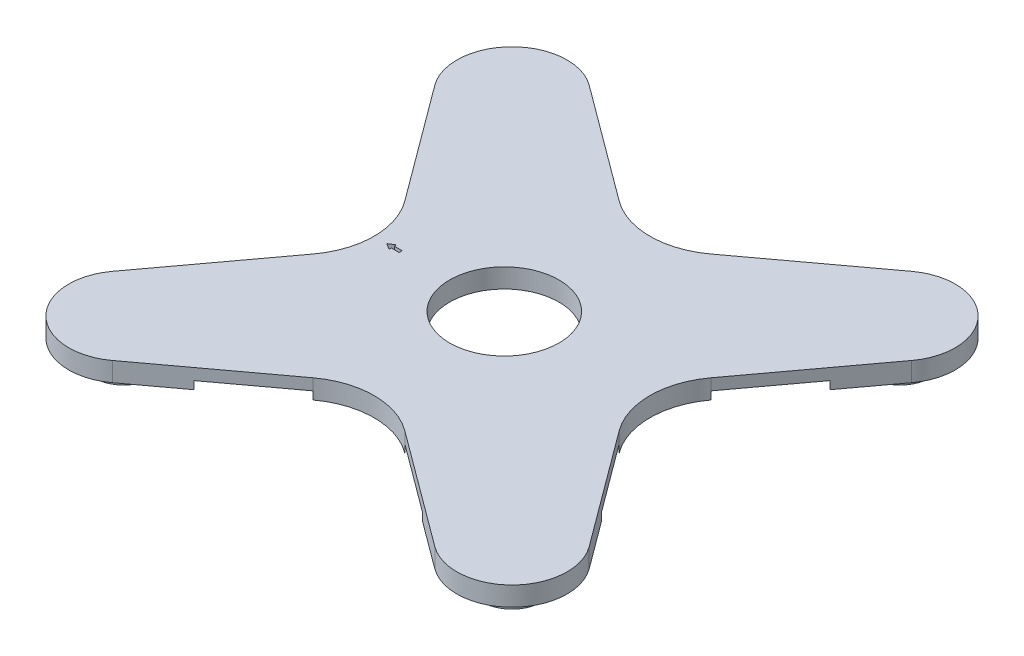
SolidWorks part; units mm, degrees
ref_plane "Front Plane" through (0, 0, 0) normal (0, 0, 1) x (1, 0, 0)
ref_plane "Top Plane" through (0, 0, 0) normal (0, 1, 0) x (1, 0, 0)
ref_plane "Right Plane" through (0, 0, 0) normal (1, 0, 0) x (0, 0, -1)
sketch "Sketch1" plane through (0, 0, 0) normal (0, 1, 0) x (1, 0, 0)
  line L0 (-25.2318, 7.5541) -> (-39.3151, 26.5872)
  line L1 (-26.5872, 39.3151) -> (-7.5541, 25.2318)
  line L2 (7.5541, 25.2318) -> (26.5872, 39.3151)
  line L3 (39.3151, 26.5872) -> (25.2318, 7.5541)
  line L4 (25.2318, -7.5541) -> (39.3151, -26.5872)
  line L5 (26.5872, -39.3151) -> (7.5541, -25.2318)
  line L6 (-7.5541, -25.2318) -> (-26.5872, -39.3151)
  line L7 (-39.3151, -26.5872) -> (-25.2318, -7.5541)
  line L8 (-32, 32) -> (32, -32) construction
  line L9 (-32, -32) -> (32, 32) construction
  line L10 (-32, -32) -> (32, -32) construction
  line L11 (-32, 32) -> (-32, -32) construction
  line L12 (-32, 32) -> (32, 32) construction
  line L13 (32, 32) -> (32, -32) construction
  line L14 (-25.2318, -7.5541) -> (-7.5541, -25.2318) construction
  line L15 (-25.2318, 7.5541) -> (-7.5541, 25.2318) construction
  line L16 (7.5541, 25.2318) -> (25.2318, 7.5541) construction
  line L17 (25.2318, -7.5541) -> (7.5541, -25.2318) construction
  line L25 (-19.6422, 0.254) -> (-18.3722, 0.254)
  line L26 (-19.6422, 0.254) -> (-19.6422, -0.254)
  line L27 (-19.6422, -0.254) -> (-18.3722, -0.254)
  line L28 (-18.3722, 0.254) -> (-18.3722, -0.254)
  line L29 (-19.6422, -0.635) -> (-20.6582, 0)
  line L30 (-20.6582, 0) -> (-19.6422, 0.635)
  line L31 (-19.6422, 0.635) -> (-19.6422, -0.635)
  circle A0 centre (0, 0) radius 7.9375 construction
  circle A1 centre (0, 0) radius 9.525 construction
  circle A2 centre (-1.27, 0) radius 9.017
  arc A3 (-39.3151, 26.5872) -> (-26.5872, 39.3151) centre (-32, 32) cw
  arc A4 (-7.5541, 25.2318) -> (7.5541, 25.2318) centre (0, 19.6422) cw
  arc A5 (26.5872, 39.3151) -> (39.3151, 26.5872) centre (32, 32) cw
  arc A6 (25.2318, 7.5541) -> (25.2318, -7.5541) centre (19.6422, 0) cw
  arc A7 (39.3151, -26.5872) -> (26.5872, -39.3151) centre (32, -32) cw
  arc A8 (7.5541, -25.2318) -> (-7.5541, -25.2318) centre (0, -19.6422) cw
  arc A9 (-26.5872, -39.3151) -> (-39.3151, -26.5872) centre (-32, -32) cw
  arc A10 (-25.2318, -7.5541) -> (-25.2318, 7.5541) centre (-19.6422, 0) cw
  circle A11 centre (-32, 32) radius 5
  circle A12 centre (32, 32) radius 5
  circle A13 centre (-32, -32) radius 5
  circle A14 centre (32, -32) radius 5
  arc A15 (-25.2318, 7.5541) -> (-25.2318, -7.5541) centre (-35.4409, 0) cw
  arc A16 (-7.5541, -25.2318) -> (7.5541, -25.2318) centre (0, -35.4409) cw
  arc A17 (-7.5541, 25.2318) -> (7.5541, 25.2318) centre (0, 35.4409) ccw
  arc A18 (25.2318, -7.5541) -> (25.2318, 7.5541) centre (35.4409, 0) cw
  point P34 (-16.3929, -16.3929)
  point P35 (16.3929, -16.3929)
  point P36 (-16.3929, 16.3929)
  point P37 (16.3929, 16.3929)
  point P38 (0, 0)
  point P47 (-19.6422, 0)
  point P51 (-19.6422, 0)
  point P52 (-19.6422, -1.0249)
  point P53 (0, 0)
  point P54 (-20.9244, 0)
  point P55 (-20.9244, 0)
  point P56 (-20.9244, 0)
  point P57 (-17.7372, -0.254)
  point P58 (-19.6422, 0)
  point P59 (-20.6582, 0)
  point P60 (-19.6422, 0.635)
  dimension "D1" = 15.875
  dimension "D2" = 19.05
  dimension "D3" = 18.034
  dimension "D6" = 10
  dimension "D9" = 12.7
  dimension "D4" = 1.27
  dimension "D5" = 64
  dimension "D7" = 18
  dimension "D8" = 25
  dimension "D10" = 0.508
  dimension "D11" = 1.27
  dimension "D12" = 1.27
  dimension "D13" = 1.016
extrude "Boss-Extrude1" add sketch "Sketch1" along normal blind 3.175 contours L4 A18 L3 A5 L2 A17 L1 A3 L0 A15 L7 A9 L6 A16 L5 A7 A14 A13 A12 A11 A2 region at (-31.339, 0, -17.7621)
extrude "Boss-Extrude2" add sketch "Sketch1<3>" against normal blind 6.35 from surface contours A11 | A14 | A12 | A13 region at (-32, 0, -32) region at (32, 0, -32) region at (-32, 0, 32) region at (32, 0, 32) starting at face at (32, 3.175, 37)
sketch "Sketch1<3>" plane through (0, 0, 0) normal (0, 1, 0) x (1, 0, 0) same geometry as "Sketch1"
sketch "Sketch2" plane through (0, 0, 0) normal (0, -1, 0) x (1, 0, 0)
  line L0 (-6.4623, -24.4239) -> (-24.4239, -6.4623)
  line L1 (-26.5872, -39.3151) -> (-7.5541, -25.2318) construction
  line L2 (-25.2318, -7.5541) -> (-39.3151, -26.5872) construction
  line L3 (-24.4239, -6.4623) -> (-33.5895, -18.8493)
  line L4 (-33.5895, -18.8493) -> (-18.8493, -33.5895)
  line L5 (-18.8493, -33.5895) -> (-6.4623, -24.4239)
  line L6 (-15.4431, -15.4431) -> (-32, -32) construction
  line L7 (3.4925, 0) -> (-3.4925, 0) construction
  line L8 (-33.5895, 18.8493) -> (-18.8493, 33.5895)
  line L9 (-24.4239, 6.4623) -> (-33.5895, 18.8493)
  line L10 (-6.4623, 24.4239) -> (-24.4239, 6.4623)
  line L11 (-18.8493, 33.5895) -> (-6.4623, 24.4239)
  line L12 (0, -3.4925) -> (0, 3.4925) construction
  line L13 (24.4239, 6.4623) -> (33.5895, 18.8493)
  line L14 (6.4623, 24.4239) -> (24.4239, 6.4623)
  line L15 (18.8493, 33.5895) -> (6.4623, 24.4239)
  line L16 (33.5895, 18.8493) -> (18.8493, 33.5895)
  line L17 (33.5895, -18.8493) -> (18.8493, -33.5895)
  line L18 (24.4239, -6.4623) -> (33.5895, -18.8493)
  line L19 (6.4623, -24.4239) -> (24.4239, -6.4623)
  line L20 (18.8493, -33.5895) -> (6.4623, -24.4239)
  circle A0 centre (-32, -32) radius 5 construction
  point P7 (0, 0)
  point P12 (-28.4645, -28.4645)
  point P13 (0, 0)
  dimension "D1" = 15.24
  dimension "D2" = 3.175
extrude "Cut-Extrude1" cut sketch "Sketch2" against normal blind 1.3
